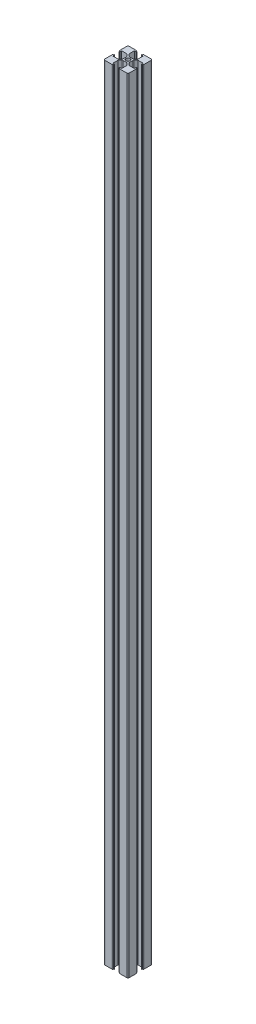
SolidWorks part; units mm, degrees
ref_plane "Front Plane" through (0, 0, 0) normal (0, 0, 1) x (1, 0, 0)
ref_plane "Top Plane" through (0, 0, 0) normal (0, 1, 0) x (1, 0, 0)
ref_plane "Right Plane" through (0, 0, 0) normal (1, 0, 0) x (0, 0, -1)
sketch "Sketch1" plane through (0, 0, 0) normal (0, 1, 0) x (1, 0, 0)
  line L0 (3.4251, 4.4858) -> (5.5, 6.5607)
  line L1 (-15, -15) -> (15, -15) construction
  line L2 (-15, -15) -> (-15, 15) construction
  line L3 (-15, 15) -> (15, 15) construction
  line L4 (15, -15) -> (15, 15) construction
  line L5 (-15, -15) -> (15, 15) construction
  line L6 (-15, 15) -> (15, -15) construction
  line L9 (0, 3.9) -> (2.0109, 3.9)
  line L10 (3.9, 0) -> (3.9, 2.0109)
  line L11 (3.9, 0) -> (3.9, -2.0109)
  line L12 (4.4858, -3.4251) -> (6.5607, -5.5)
  line L13 (4.4858, 3.4251) -> (6.5607, 5.5)
  line L14 (5.5, 13.2) -> (3.1, 13.2)
  line L15 (3.1, 13.2) -> (3.1, 14.24)
  line L16 (5.5, 13.2) -> (5.5, 6.5607)
  line L17 (13.2, 5.5) -> (6.5607, 5.5)
  line L21 (4.1, 15) -> (4.1, 14.24)
  line L22 (13.2, 5.5) -> (13.2, 3.1)
  line L23 (13.2, 3.1) -> (14.24, 3.1)
  line L24 (14.24, 3.1) -> (14.24, 4.1)
  line L25 (15, 4.1) -> (14.24, 4.1)
  line L26 (0, 0) -> (50000, 0) construction
  line L27 (0, 0) -> (0, -50000) construction
  line L28 (4.1, 15) -> (13.5, 15)
  line L29 (15, 13.5) -> (15, 4.1)
  line L30 (4.1, 14.24) -> (3.1, 14.24)
  line L31 (13.2, -5.5) -> (6.5607, -5.5)
  line L32 (13.2, -5.5) -> (13.2, -3.1)
  line L33 (13.2, -3.1) -> (14.24, -3.1)
  line L34 (14.24, -4.1) -> (14.24, -3.1)
  line L35 (15, -4.1) -> (14.24, -4.1)
  line L36 (15, -4.1) -> (15, -13.5)
  line L37 (13.5, -15) -> (4.1, -15)
  line L38 (4.1, -15) -> (4.1, -14.24)
  line L39 (3.1, -14.24) -> (4.1, -14.24)
  line L40 (3.1, -13.2) -> (3.1, -14.24)
  line L41 (5.5, -13.2) -> (3.1, -13.2)
  line L42 (5.5, -13.2) -> (5.5, -6.5607)
  line L43 (3.4251, -4.4858) -> (5.5, -6.5607)
  line L44 (0, -3.9) -> (2.0109, -3.9)
  line L45 (0, -3.9) -> (-2.0109, -3.9)
  line L46 (-3.4251, -4.4858) -> (-5.5, -6.5607)
  line L47 (-5.5, -13.2) -> (-5.5, -6.5607)
  line L48 (-5.5, -13.2) -> (-3.1, -13.2)
  line L49 (-3.1, -13.2) -> (-3.1, -14.24)
  line L50 (-4.1, -14.24) -> (-3.1, -14.24)
  line L51 (-4.1, -15) -> (-4.1, -14.24)
  line L52 (-4.1, -15) -> (-13.5, -15)
  line L53 (-15, -13.5) -> (-15, -4.1)
  line L54 (-15, -4.1) -> (-14.24, -4.1)
  line L55 (-14.24, -3.1) -> (-14.24, -4.1)
  line L56 (-13.2, -3.1) -> (-14.24, -3.1)
  line L57 (-13.2, -5.5) -> (-13.2, -3.1)
  line L58 (-13.2, -5.5) -> (-6.5607, -5.5)
  line L59 (-4.4858, -3.4251) -> (-6.5607, -5.5)
  line L60 (-3.9, 0) -> (-3.9, -2.0109)
  line L61 (-3.9, 0) -> (-3.9, 2.0109)
  line L62 (-4.4858, 3.4251) -> (-6.5607, 5.5)
  line L63 (-13.2, 5.5) -> (-6.5607, 5.5)
  line L64 (-13.2, 5.5) -> (-13.2, 3.1)
  line L65 (-13.2, 3.1) -> (-14.24, 3.1)
  line L66 (-14.24, 4.1) -> (-14.24, 3.1)
  line L67 (-15, 4.1) -> (-14.24, 4.1)
  line L68 (-15, 4.1) -> (-15, 13.5)
  line L69 (-13.5, 15) -> (-4.1, 15)
  line L70 (-4.1, 15) -> (-4.1, 14.24)
  line L71 (-3.1, 14.24) -> (-4.1, 14.24)
  line L72 (-3.1, 13.2) -> (-3.1, 14.24)
  line L73 (-5.5, 13.2) -> (-3.1, 13.2)
  line L74 (-5.5, 13.2) -> (-5.5, 6.5607)
  line L75 (-3.4251, 4.4858) -> (-5.5, 6.5607)
  line L76 (0, 3.9) -> (-2.0109, 3.9)
  arc A1 (3.9, 2.0109) -> (4.4858, 3.4251) centre (5.9, 2.0109) cw
  arc A2 (3.4251, 4.4858) -> (2.0109, 3.9) centre (2.0109, 5.9) cw
  arc A3 (15, 13.5) -> (13.5, 15) centre (13.5, 13.5) ccw
  arc A4 (2.5, 0) -> (0, 2.5) centre (0, 0) ccw
  arc A5 (0, -2.5) -> (2.5, 0) centre (0, 0) ccw
  arc A6 (4.4858, -3.4251) -> (3.9, -2.0109) centre (5.9, -2.0109) cw
  arc A7 (13.5, -15) -> (15, -13.5) centre (13.5, -13.5) ccw
  arc A8 (2.0109, -3.9) -> (3.4251, -4.4858) centre (2.0109, -5.9) cw
  arc A9 (-2.5, 0) -> (0, -2.5) centre (0, 0) ccw
  arc A10 (-3.4251, -4.4858) -> (-2.0109, -3.9) centre (-2.0109, -5.9) cw
  arc A11 (-15, -13.5) -> (-13.5, -15) centre (-13.5, -13.5) ccw
  arc A12 (-3.9, -2.0109) -> (-4.4858, -3.4251) centre (-5.9, -2.0109) cw
  arc A13 (0, 2.5) -> (-2.5, 0) centre (0, 0) ccw
  arc A14 (-4.4858, 3.4251) -> (-3.9, 2.0109) centre (-5.9, 2.0109) cw
  arc A15 (-13.5, 15) -> (-15, 13.5) centre (-13.5, 13.5) ccw
  arc A16 (-2.0109, 3.9) -> (-3.4251, 4.4858) centre (-2.0109, 5.9) cw
  point P0 (0, 0)
  point P30 (3.1, 15)
  point P115 (0, 0)
  dimension "D2" = 2.5
  dimension "D3" = 2
  dimension "D12" = 1.5
  dimension "D1" = 30
  dimension "D4" = 1.5
  dimension "D5" = 1.8
  dimension "D6" = 5.5
  dimension "D7" = 0.76
  dimension "D8" = 3.1
  dimension "D9" = 1
  dimension "D10" = 3.9
  dimension "D11" = 3.9
  dimension "D13" = 4
extrude "Boss-Extrude1" add sketch "Sketch1" along normal blind 965.2 contours L76 A16 L75 L74 L73 L72 L71 L70 L69 A15 L68 L67 L66 L65 L64 L63 L62 A14 L61 L60 A12 L59 L58 L57 L56 L55 L54 L53 A11 L52 L51 L50 L49 L48 L47 L46 A10 L45 L44 A8 L43 L42 L41 L40 L39 L38 L37 A7 L36 L35 L34 region at (4.7626, 0, -5.2232)
fillet "Fillet1" radius 0.35 33 edges at (-4.1, 482.6, -15) (-4.1, 482.6, -14.24) (-3.1, 482.6, -14.24) (-3.1, 482.6, -13.2) (-14.24, 482.6, -4.1) (-15, 482.6, -4.1) (-14.24, 482.6, -3.1) (-13.2, 482.6, -3.1) (-15, 482.6, 4.1) (-14.24, 482.6, 4.1) (-14.24, 482.6, 3.1) (-13.2, 482.6, 3.1) (-4.1, 482.6, 15) (-4.1, 482.6, 14.24) (-3.1, 482.6, 14.24) (-3.1, 482.6, 13.2) (4.1, 482.6, 15) (4.1, 482.6, 14.24) (3.1, 482.6, 14.24) (3.1, 482.6, 13.2) (15, 482.6, 4.1) (14.24, 482.6, 4.1) (14.24, 482.6, 3.1) (13.2, 482.6, 3.1) (15, 482.6, -4.1) (14.24, 482.6, -4.1) (14.24, 482.6, -3.1) (13.2, 482.6, -3.1) (3.1, 482.6, -13.2) (4.1, 482.6, -15) (5.5, 482.6, -6.5607) (3.1, 482.6, -14.24) (4.1, 482.6, -14.24)
